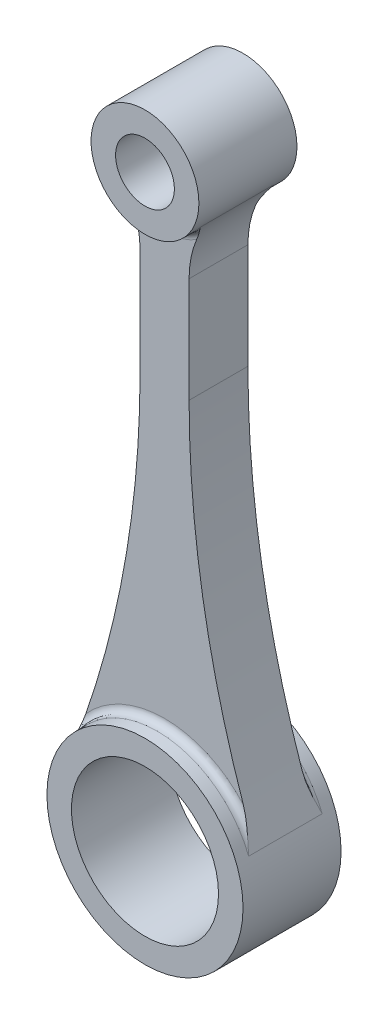
SolidWorks part; units mm, degrees
ref_plane "Płaszczyzna przednia" through (0, 0, 0) normal (0, 0, 1) x (1, 0, 0)
ref_plane "Płaszczyzna górna" through (0, 0, 0) normal (0, 1, 0) x (1, 0, 0)
ref_plane "Płaszczyzna prawa" through (0, 0, 0) normal (1, 0, 0) x (0, 0, -1)
sketch "Szkic1" plane through (0, 0, 0) normal (0, 0, 1) x (1, 0, 0)
  circle A0 centre (0, 0) radius 15
  circle A1 centre (0, 0) radius 20
  circle A2 centre (0, 120) radius 6
  circle A3 centre (0, 120) radius 11
  dimension "D2" = 12
  dimension "D3" = 22
  dimension "D4" = 30
  dimension "D5" = 40
  dimension "D1" = 120
extrude "Dodanie-wyciągnięcie1" add sketch "Szkic1" along normal mid plane 20
sketch "Szkic2" plane through (0, 0, 0) normal (0, 0, 1) x (1, 0, 0)
  line L2 (0, 0) -> (0, 120) construction
  line L3 (-5, 110.202) -> (-5, 80.202)
  line L4 (5, 80.202) -> (5, 110.202)
  circle A0 centre (0, 120) radius 11 construction
  arc A1 (-5, 80.202) -> (-18.6481, 7.2283) centre (-206.9122, 80.202) cw
  circle A2 centre (0, 0) radius 20 construction
  arc A3 (-18.6481, 7.2283) -> (18.6481, 7.2283) centre (0, 0) cw
  arc A4 (18.6481, 7.2283) -> (5, 80.202) centre (206.9122, 80.202) cw
  arc A6 (-5, 110.202) -> (5, 110.202) centre (0, 120) ccw
  dimension "D1" = 5
  dimension "D2" = 30
extrude "Dodanie-wyciągnięcie2" add sketch "Szkic2" along normal mid plane 12
fillet "Zaokrąglenie1" radius 1.5 4 edges at (0, 20, -6) (0, 20, 6) (0, 109, -6) (0, 109, 6)
fillet "Zaokrąglenie2" radius 20 2 edges at (-5, 110.202, 0) (5, 110.202, 0)
